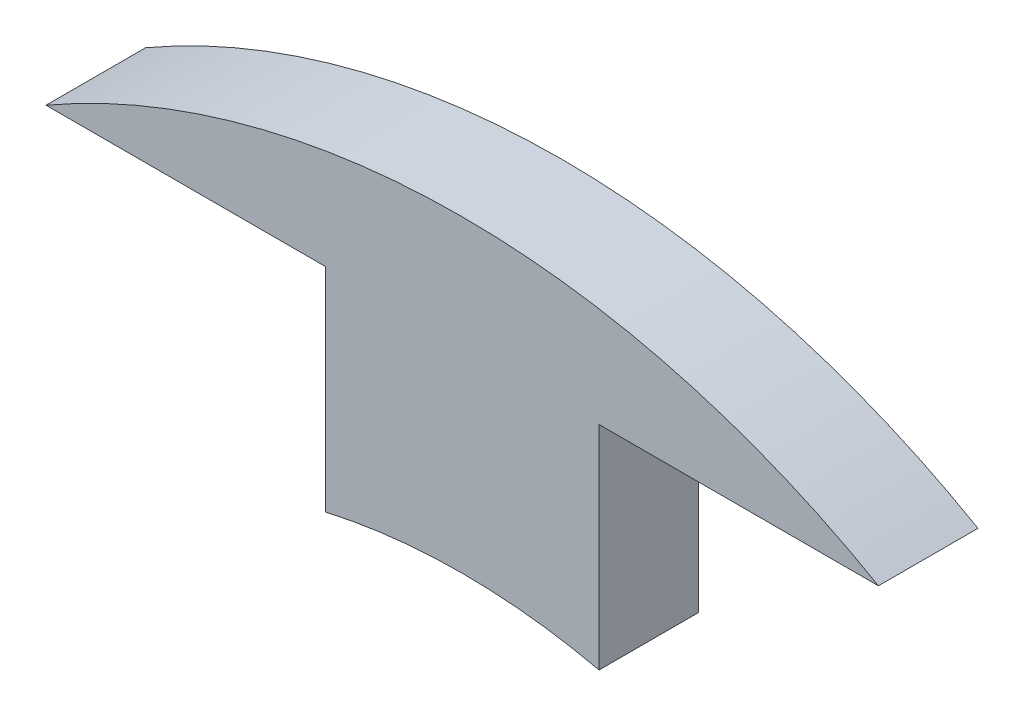
SolidWorks part; units mm, degrees
ref_plane "Front Plane" through (0, 0, 0) normal (0, 0, 1) x (1, 0, 0)
ref_plane "Top Plane" through (0, 0, 0) normal (0, 1, 0) x (1, 0, 0)
ref_plane "Right Plane" through (0, 0, 0) normal (1, 0, 0) x (0, 0, -1)
sketch "Sketch4" plane through (0, 0, 0) normal (0, 0, 1) x (1, 0, 0)
  line L4 (-12.6641, 24.75) -> (-4.1641, 24.75)
  line L5 (-4.1641, 24.75) -> (-4.1641, 18.2818)
  line L6 (4.1641, 24.75) -> (4.1641, 18.2818)
  line L7 (12.6641, 24.75) -> (4.1641, 24.75)
  arc A0 (4.1641, 18.2818) -> (-4.1641, 18.2818) centre (0, 0) ccw
  arc A1 (-12.6641, 24.75) -> (12.6641, 24.75) centre (0, 2.8151) cw
  point P8 (0, 18.75)
  dimension "D1" = 18.75
  dimension "D3" = 25.3282
  dimension "D2" = 6.4682
  dimension "D5" = 8.5
extrude "Boss-Extrude1" add sketch "Sketch4" along normal blind 3.03
